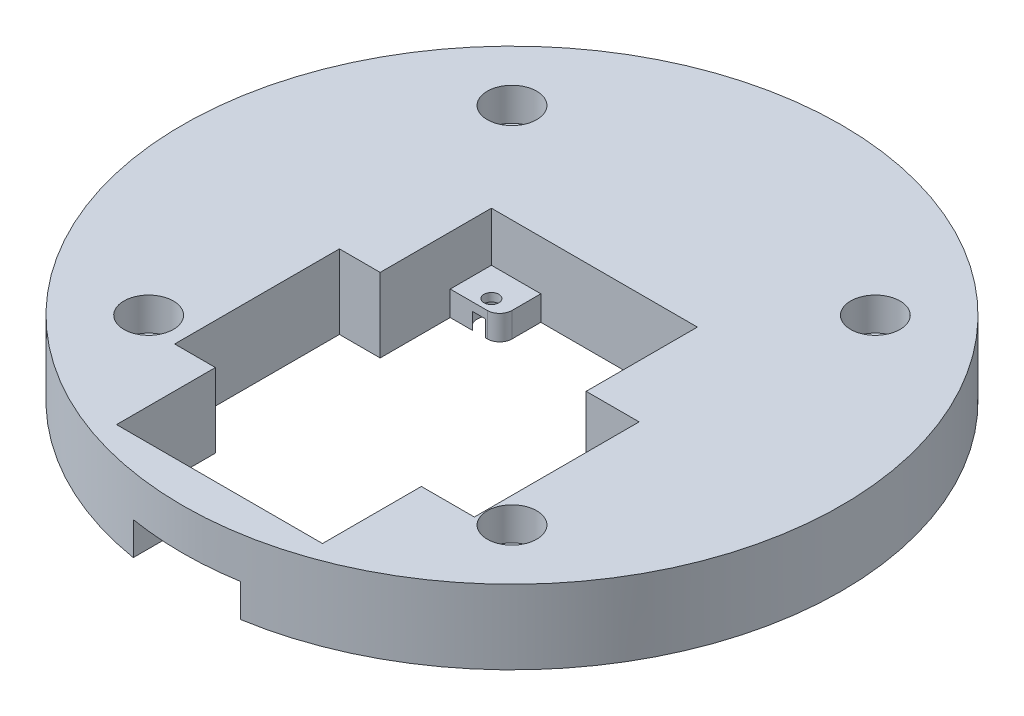
SolidWorks part; units mm, degrees
note: '?' marks a value the reader was unsure of.
ref_plane "Front Plane" through (0, 0, 0) normal (0, 0, 1) x (1, 0, 0)
ref_plane "Top Plane" through (0, 0, 0) normal (0, 1, 0) x (1, 0, 0)
ref_plane "Right Plane" through (0, 0, 0) normal (1, 0, 0) x (0, 0, -1)
sketch "Sketch1" plane through (0, 0, 0) normal (0, 1, 0) x (1, 0, 0)
  circle A0 centre (0, 0) radius 40
extrude "Boss-Extrude1" add sketch "Sketch1" along normal blind 8 and the other way blind 1
sketch "Sketch2" plane through (0, 8, 0) normal (0, 1, 0) x (1, 0, 0)
  line L1 (-12.5, 10) -> (12.5, 10)
  line L2 (-12.5, 10) -> (-12.5, -35.5)
  line L3 (-12.5, -35.5) -> (12.5, -35.5)
  line L4 (12.5, 10) -> (12.5, -35.5)
  point P7 (1.8246, -22.3861)
  dimension "D1" = 10
  dimension "D2" = 35.5
  dimension "D3" = 12.5
  dimension "D4" = 25
extrude "Cut-Extrude1" cut sketch "Sketch2" against normal blind 6
sketch "Sketch3" plane through (0, 2, 0) normal (0, 1, 0) x (1, 0, 0)
  line L0 (-12.5, 10) -> (-12.5, -35.5) construction
  line L1 (-12.5, 5) -> (-6.5, 5)
  line L2 (-12.5, 5) -> (-12.5, -30.5)
  line L3 (-12.5, -30.5) -> (-6.5, -30.5)
  line L4 (12.5, 5) -> (12.5, -30.5)
  line L5 (12.5, -35.5) -> (12.5, 10) construction
  line L6 (12.5, 10) -> (-12.5, 10) construction
  line L7 (-12.5, -35.5) -> (12.5, -35.5) construction
  line L8 (0, 37.3302) -> (0, -8.1698) construction
  line L9 (-6.5, 10) -> (6.5, 10)
  line L10 (-6.5, 10) -> (-6.5, 5)
  line L11 (-6.5, -35.5) -> (6.5, -35.5)
  line L12 (6.5, 10) -> (6.5, 5)
  line L13 (6.5, 5) -> (12.5, 5)
  line L14 (6.5, -30.5) -> (6.5, -35.5)
  line L15 (-6.5, -30.5) -> (-6.5, -35.5)
  line L16 (6.5, -30.5) -> (12.5, -30.5)
  dimension "D1" = 5
  dimension "D2" = 5
  dimension "D3" = 13
extrude "Cut-Extrude2" cut sketch "Sketch3" against normal blind 6
sketch "Sketch4" plane through (0, 8, 0) normal (0, 1, 0) x (1, 0, 0)
  line L0 (-43.7365, 0) -> (63.2413, 0) construction
  line L1 (0, 0) -> (36.7999, -36.7999) construction
  circle A0 centre (22.0512, -22.0512) radius 3
  dimension "D2" = 6
  dimension "D1" = 45
extrude "Cut-Extrude3" cut sketch "Sketch4" against normal blind 4
sketch "Sketch5" plane through (0, 4, 0) normal (0, 1, 0) x (1, 0, 0)
  circle A0 centre (22.0512, -22.0512) radius 1.4
extrude "Cut-Extrude4" cut sketch "Sketch5" against normal up to next
ref_axis "Axis2" through (0, 0, 0) along (0, 1, 0)?
pattern_circular "CirPattern1" count 4 every 90 about axis through (0, 0, 0) along (0, 1, 0) of "Cut-Extrude3", "Cut-Extrude4"
fillet "Fillet1" radius 1.5 4 edges at (-6.5, 0.5, 30.5) (6.5, 0.5, 30.5) (6.5, 0.5, -5) (-6.5, 0.5, -5)
sketch "Sketch6" plane through (0, -1, 0) normal (0, -1, 0) x (1, 0, 0)
  line L1 (6.5, 35.5) -> (-6.5, 35.5)
  line L2 (6.5, 35.5) -> (6.5, 44.1868)
  line L3 (6.5, 44.1868) -> (-6.5, 44.1868)
  line L4 (-6.5, 35.5) -> (-6.5, 44.1868)
extrude "Cut-Extrude5" cut sketch "Sketch6" against normal blind 4
sketch "Sketch7" plane through (0, -1, 0) normal (0, -1, 0) x (1, 0, 0)
  line L0 (-6.5, 35.5) -> (6.5, 35.5) construction
  line L1 (-17.4474, 23.5) -> (18.9299, 23.5)
  line L2 (-17.4474, 23.5) -> (-17.4474, 3.5)
  line L3 (-17.4474, 3.5) -> (18.9299, 3.5)
  line L4 (18.9299, 23.5) -> (18.9299, 3.5)
  dimension "D1" = 12
  dimension "D2" = 20
extrude "Cut-Extrude6" cut sketch "Sketch7" against normal up to next
sketch "Sketch8" plane through (0, 2, 0) normal (0, 1, 0) x (1, 0, 0)
  line L0 (0, 17.2017) -> (0, -63.3124) construction
  line L1 (-49.3806, 0) -> (60.5468, 0) construction
  circle A0 centre (9, -32) radius 0.9
  circle A1 centre (-9, -32) radius 0.9
  circle A2 centre (-9, 6.5) radius 0.9
  circle A3 centre (9, 6.5) radius 0.9
  point P15 (0, 0)
  dimension "D1" = 32
  dimension "D3" = 9
  dimension "D5" = 1.8
  dimension "D8" = 6.5
  dimension "D2" = 9
  dimension "D4" = 32
  dimension "D6" = 6.5
  dimension "D7" = 9
  dimension "D9" = 9
extrude "Cut-Extrude7" cut sketch "Sketch8" against normal blind 4
sketch "Sketch9" plane through (0, -1, 0) normal (0, -1, 0) x (1, 0, 0)
  circle A0 centre (-9, -6.5) radius 1.7
  circle A1 centre (9, -6.5) radius 1.7
  circle A2 centre (9, 32) radius 1.7
  circle A3 centre (-9, 32) radius 1.7
extrude "Cut-Extrude10" cut sketch "Sketch9" against normal blind 2
